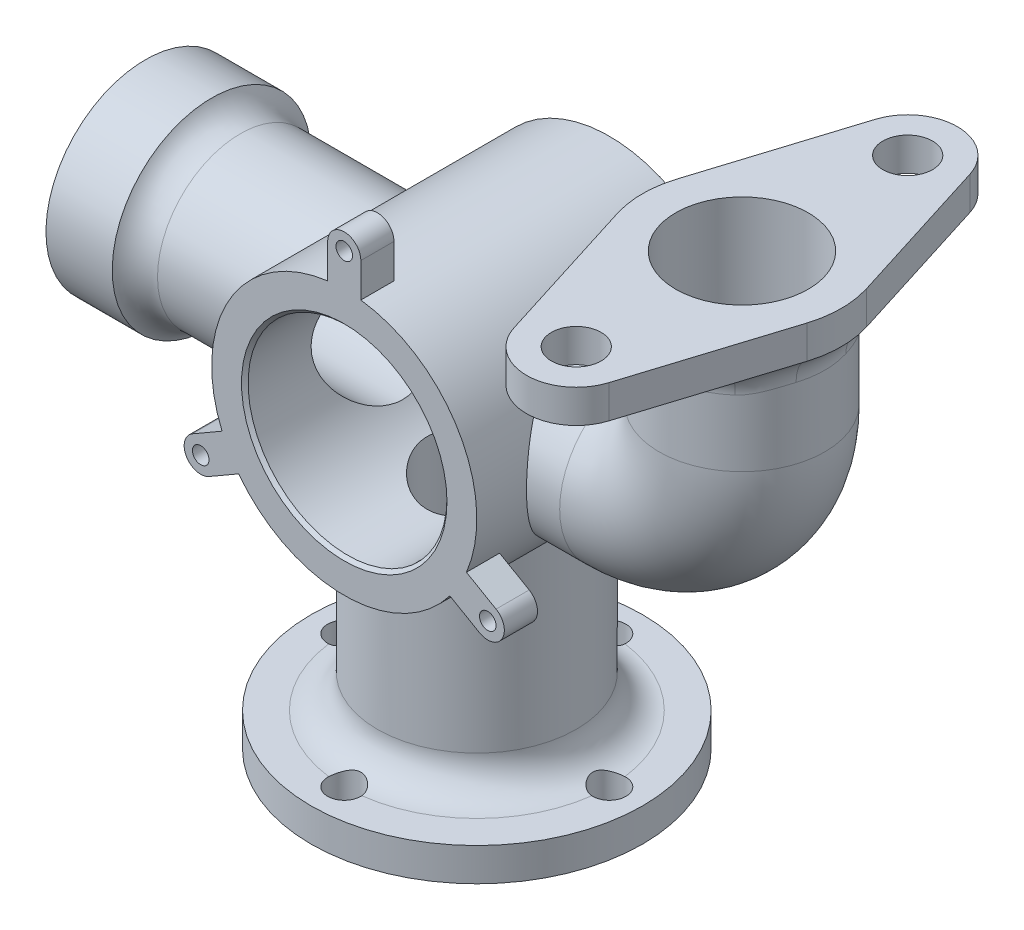
SolidWorks part; units mm, degrees
note: The reader was unsure of these and kept them because the rebuilt part matched: shared geometry of "Sketch2<3>".
material "Ti-5Al-2.5Sn Annealed (SS)"
ref_plane "Front Plane" through (0, 0, 0) normal (0, 0, 1) x (1, 0, 0)
ref_plane "Top Plane" through (0, 0, 0) normal (0, 1, 0) x (1, 0, 0)
ref_plane "Right Plane" through (0, 0, 0) normal (1, 0, 0) x (0, 0, -1)
sketch "Sketch1" plane through (0, 0, 0) normal (0, 0, 1) x (1, 0, 0)
  circle A0 centre (0, 0) radius 40
  dimension "D1" = 80
extrude "Boss-Extrude1" add sketch "Sketch1" along normal mid plane 80
sketch "Sketch2" plane through (0, 0, 0) normal (0, 0, 1) x (1, 0, 0)
  line L0 (-100, 0) -> (50, 0)
  line L1 (80, 30) -> (80, 70)
  arc A0 (80, 30) -> (50, 0) centre (50, 30) cw
  point P6 (80, 0)
  dimension "D4" = 30
  dimension "D1" = 180
  dimension "D2" = 70
  dimension "D3" = 100
ref_plane "Plane1" through (80, 70, 0) normal (0, 1, 0) x (1, 0, 0)
sketch "Sketch3" plane through (80, 70, 0) normal (0, 1, 0) x (1, 0, 0)
  circle A0 centre (0, 0) radius 25
  dimension "D1" = 50
sweep "Sweep1" add profiles "Sketch3" path "Sketch2"
sketch "Sketch4" plane through (0, 0, 40) normal (0, 0, 1) x (1, 0, 0)
  circle A0 centre (0, 0) radius 30
  dimension "D1" = 60
extrude "Cut-Extrude1" cut sketch "Sketch4" against normal blind 70
sketch "Sketch5" plane through (-100, 0, 0) normal (-1, 0, 0) x (0, 0, 1)
  circle A0 centre (0, 0) radius 30
  dimension "D1" = 60
extrude "Boss-Extrude2" add sketch "Sketch5" against normal blind 20
sketch "Sketch6" plane through (0, 70, 0) normal (0, 1, 0) x (1, 0, 0)
  line L0 (80, 50) -> (80, -50) construction
  line L1 (94.3091, 54.5) -> (108.6182, 9)
  line L2 (65.6909, 54.5) -> (51.3818, 9)
  line L3 (39.4091, 0) -> (130.1969, 0) construction
  line L4 (65.6909, -54.5) -> (51.3818, -9)
  line L5 (94.3091, -54.5) -> (108.6182, -9)
  circle A0 centre (80, 0) radius 30
  circle A1 centre (80, 50) radius 15
  circle A2 centre (80, 50) radius 7.5
  circle A3 centre (80, -50) radius 7.5
  circle A4 centre (80, -50) radius 15
  circle M1 centre (80, 0) radius 25
  dimension "D1" = 100
  dimension "D2" = 15
  dimension "D3" = 30
  dimension "D4" = 60
extrude "Boss-Extrude3" add sketch "Sketch6" against normal blind 10 contours A1 A2 | A1 L2 A0 L1 | M1 | A0 M1 | L4 A4 L5 A0 | A4 A3
sketch "Sketch7" plane through (0, 70, 0) normal (0, 1, 0) x (1, 0, 0)
  circle A0 centre (80, 0) radius 20
  dimension "D1" = 40
sweep "Cut-Sweep1" cut profiles "Sketch7" path "Sketch2<3>"
sketch "Sketch2<3>" plane through (0, 0, 0) normal (0, 0, 1) x (1, 0, 0) same geometry as "Sketch2"
fillet "Fillet1" radius 10 2 edges at (80, 60, 25) (-80, -25, 0)
chamfer "Chamfer1" distance 1 angle 45 1 edges at (30, 0, 40)
sketch "Sketch8" plane through (0, 0, 40) normal (0, 0, 1) x (1, 0, 0)
  line L0 (5, 50) -> (5, 39.6863)
  line L1 (-5, 50) -> (-5, 39.6863)
  line L2 (45.8013, -20.6699) -> (36.8693, -15.513)
  line L3 (40.8013, -29.3301) -> (31.8693, -24.1733)
  line L4 (-40.8013, -29.3301) -> (-31.8693, -24.1733)
  line L5 (-45.8013, -20.6699) -> (-36.8693, -15.513)
  circle A0 centre (0, 0) radius 50 construction
  circle A1 centre (0, 50) radius 5
  circle A2 centre (0, 50) radius 2.5
  circle A3 centre (0, 0) radius 40 construction
  circle A4 centre (0, 0) radius 40
  circle A5 centre (43.3013, -25) radius 5
  circle A6 centre (43.3013, -25) radius 2.5
  circle A7 centre (-43.3013, -25) radius 5
  circle A8 centre (-43.3013, -25) radius 2.5
  circle A9 centre (0, 0) radius 31 construction
  point P29 (0, 0)
  circle M2 centre (0, 0) radius 40
  dimension "D1" = 100
  dimension "D2" = 10
  dimension "D3" = 5
  dimension "D4" = 3
extrude "Boss-Extrude4" add sketch "Sketch8" against normal blind 10 contours A1 L1 L0 M2 | A1 A2 | A7 L4 L5 M2 | A7 A8 | A5 L2 L3 M2 | A5 A6
ref_plane "Plane2" through (0, -100, 0) normal (0, 1, 0) x (1, 0, 0)
sketch "Sketch9" plane through (0, -100, 0) normal (0, 1, 0) x (1, 0, 0)
  circle A0 centre (0, 0) radius 50
  circle A1 centre (0, 0) radius 40 construction
  circle A2 centre (0, 40) radius 5
  circle A3 centre (40, 0) radius 5
  circle A4 centre (0, -40) radius 5
  circle A5 centre (-40, 0) radius 5
  point P15 (0, 0)
  dimension "D1" = 80
  dimension "D2" = 100
  dimension "D3" = 4
  dimension "D4" = 10
extrude "Boss-Extrude5" add sketch "Sketch9" along normal blind 10 separate body
sketch "Sketch11" plane through (0, -90, 0) normal (0, 1, 0) x (1, 0, 0)
  circle A0 centre (0, 0) radius 30
  dimension "D1" = 60
extrude "Boss-Extrude6" add sketch "Sketch11" along normal up to surface (50 mm away)
sketch "Sketch12" plane through (0, -100, 0) normal (0, -1, 0) x (1, 0, 0)
  circle A0 centre (0, 0) radius 15
  dimension "D1" = 30
extrude "Cut-Extrude2" cut sketch "Sketch12" against normal up to surface (70 mm away)
fillet "Fillet2" radius 10 1 edges at (0, -90, 30)
